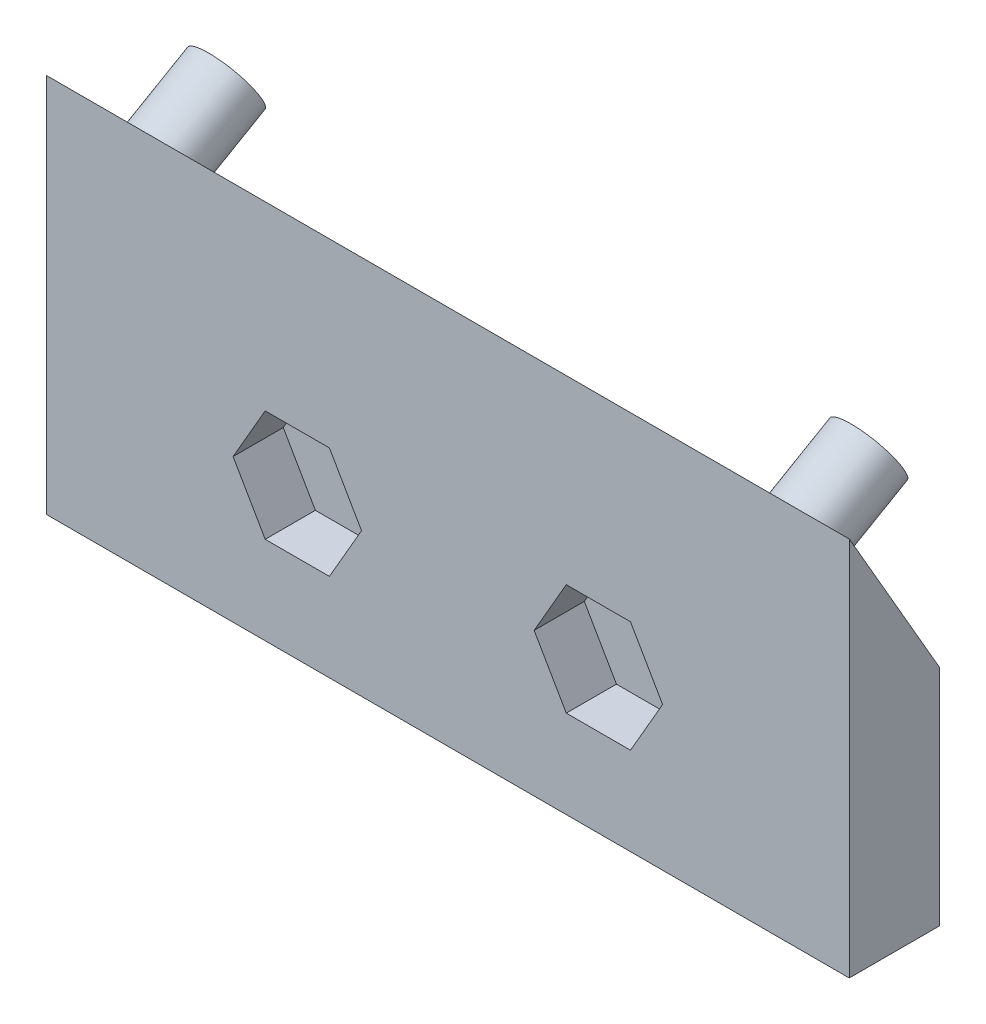
SolidWorks part; units mm, degrees
ref_plane "Front Plane" through (0, 0, 0) normal (0, 0, 1) x (1, 0, 0)
ref_plane "Top Plane" through (0, 0, 0) normal (0, 1, 0) x (1, 0, 0)
ref_plane "Right Plane" through (0, 0, 0) normal (1, 0, 0) x (0, 0, -1)
ref_plane "Plane1" through (-82, -11.15, 0) normal (0, 0, -1) x (-1, 0, 0)
sketch "Sketch3" plane through (0, 0, 0) normal (0, 0, 1) x (1, 0, 0)
  line L0 (-42, 0) -> (-42, -11.15)
  line L22 (-58.75, 0) -> (-58.75, -4)
  line L23 (-65.25, -4) -> (-65.25, 0)
  line L24 (-65.25, 0) -> (-67.85, 0)
  line L25 (-67.85, 0) -> (-67.85, -4)
  line L26 (-71.15, -4) -> (-71.15, 0)
  line L27 (-71.15, 0) -> (-82, 0)
  line L28 (-82, 0) -> (-82, -11.15)
  line L29 (-82, -11.15) -> (0, -11.15)
  line L30 (0, -11.15) -> (0, 0)
  line L31 (0, 0) -> (-10.85, 0)
  line L32 (-10.85, 0) -> (-10.85, -4)
  line L33 (-14.15, -4) -> (-14.15, 0)
  line L34 (-14.15, 0) -> (-16.75, 0)
  line L35 (-16.75, 0) -> (-16.75, -4)
  line L36 (-23.25, -4) -> (-23.25, 0)
  line L37 (-23.25, 0) -> (-25.85, 0)
  line L38 (-25.85, 0) -> (-25.85, -4)
  line L39 (-29.15, -4) -> (-29.15, 0)
  line L40 (-29.15, 0) -> (-52.85, 0)
  line L41 (-52.85, 0) -> (-52.85, -4)
  line L42 (-56.15, -4) -> (-56.15, 0)
  line L43 (-56.15, 0) -> (-58.75, 0)
  line L49 (-42, 0) -> (-82, 0)
  line L50 (-82, 0) -> (-82, -11.15)
  line L51 (-82, -11.15) -> (-42, -11.15)
  circle A0 centre (-69.5, -4) radius 1.65
  circle A1 centre (-54.5, -4) radius 1.65
  arc A6 (-65.25, -4) -> (-58.75, -4) centre (-62, -4) ccw
  arc A7 (-71.15, -4) -> (-67.85, -4) centre (-69.5, -4) ccw
  arc A8 (-14.15, -4) -> (-10.85, -4) centre (-12.5, -4) ccw
  arc A9 (-23.25, -4) -> (-16.75, -4) centre (-20, -4) ccw
  arc A10 (-29.15, -4) -> (-25.85, -4) centre (-27.5, -4) ccw
  arc A11 (-56.15, -4) -> (-52.85, -4) centre (-54.5, -4) ccw
  arc A13 (-71.15, -4) -> (-67.85, -4) centre (-69.5, -4) ccw construction
  arc A17 (-56.15, -4) -> (-52.85, -4) centre (-54.5, -4) ccw construction
  dimension "D1" = 0
extrude "Boss-Extrude1" add sketch "Sketch3" along normal blind 2 contours L0 L51 L50 L49 | A1 | A0
sketch "Sketch4" plane through (0, 0, 2) normal (0, 0, 1) x (1, 0, 0)
  line L0 (-42, 0) -> (-82, 0) construction
  line L1 (-71.1, -1.2287) -> (-72.7, -4)
  line L2 (-72.7, -4) -> (-71.1, -6.7713)
  line L3 (-71.1, -6.7713) -> (-67.9, -6.7713)
  line L4 (-67.9, -6.7713) -> (-66.3, -4)
  line L5 (-66.3, -4) -> (-67.9, -1.2287)
  line L6 (-67.9, -1.2287) -> (-71.1, -1.2287)
  line L7 (-56.1, -1.2287) -> (-57.7, -4)
  line L8 (-57.7, -4) -> (-56.1, -6.7713)
  line L9 (-56.1, -6.7713) -> (-52.9, -6.7713)
  line L10 (-52.9, -6.7713) -> (-51.3, -4)
  line L11 (-51.3, -4) -> (-52.9, -1.2287)
  line L12 (-52.9, -1.2287) -> (-56.1, -1.2287)
  line L13 (-82, 0) -> (-82, -11.15) construction
  line L14 (-82, -11.15) -> (-42, -11.15) construction
  line L15 (-42, 0) -> (-42, -11.15) construction
  line L16 (-42, 0) -> (-82, 0)
  line L17 (-82, 0) -> (-82, -11.15)
  line L18 (-82, -11.15) -> (-42, -11.15)
  line L19 (-42, 0) -> (-42, -11.15)
  circle A0 centre (-69.5, -4) radius 3.2 construction
  circle A1 centre (-54.5, -4) radius 3.2 construction
  dimension "D1" = 6.4
  dimension "D2" = 6.4
extrude "Boss-Extrude2" add sketch "Sketch4" along normal blind 2.5
sketch "Sketch5" plane through (-82, 0, 0) normal (-1, 0, 0) x (0, 0, 1)
  line L4 (0, 0) -> (4.5, 7.7942)
  line L5 (4.5, 7.7942) -> (4.5, 0)
  line L6 (4.5, 0) -> (0, 0)
  dimension "D2" = 60
extrude "Boss-Extrude3" add sketch "Sketch5" against normal up to surface (40 mm away) up to face at (-42, -5.575, 2.25)
ref_plane "Plane2" through (-62, 0, 0) normal (1, 0, 0) x (0, 0, -1)
sketch "Sketch7" plane through (0, 0, 0) normal (0, 0.5, -0.866) x (-1, 0, 0)
  line L0 (42, 0) -> (82, 0) construction
  line L1 (82, 9) -> (82, 0) construction
  circle A0 centre (78, 6) radius 1.75
  dimension "D1" = 3.5
  dimension "D2" = 4
  dimension "D3" = 6
extrude "Boss-Extrude5" add sketch "Sketch7" along normal blind 4
mirror "Mirror2" about plane through (-62, 0, 0) normal (1, 0, 0) of "Boss-Extrude5"
sketch "Sketch8" plane through (0, 0, 2) normal (0, 0, 1) x (1, 0, 0)
  line L6 (-67.9, -1.2287) -> (-71.1, -1.2287)
  line L7 (-71.1, -1.2287) -> (-72.7, -4)
  line L8 (-72.7, -4) -> (-71.1, -6.7713)
  line L9 (-71.1, -6.7713) -> (-67.9, -6.7713)
  line L10 (-67.9, -6.7713) -> (-66.3, -4)
  line L11 (-66.3, -4) -> (-67.9, -1.2287)
  line L12 (-67.9, -1.2287) -> (-71.1, -1.2287)
  line L13 (-71.1, -1.2287) -> (-72.7, -4)
  line L14 (-72.7, -4) -> (-71.1, -6.7713)
  line L15 (-71.1, -6.7713) -> (-67.9, -6.7713)
  line L16 (-67.9, -6.7713) -> (-66.3, -4)
  line L17 (-66.3, -4) -> (-67.9, -1.2287)
  circle A0 centre (-54.5, -4) radius 1.65 construction
  circle A1 centre (-54.5, -4) radius 1.65
  circle A2 centre (-69.5, -4) radius 1.65 construction
  circle A3 centre (-69.5, -4) radius 1.65
  circle M13 centre (-69.5, -4) radius 1.65
  dimension "D1" = 0
extrude "Boss-Extrude6" add sketch "Sketch8" against normal blind 0.5 contours M13 | A1 region at (-54.5, -4, 2) region at (-69.5, -4, 2)
